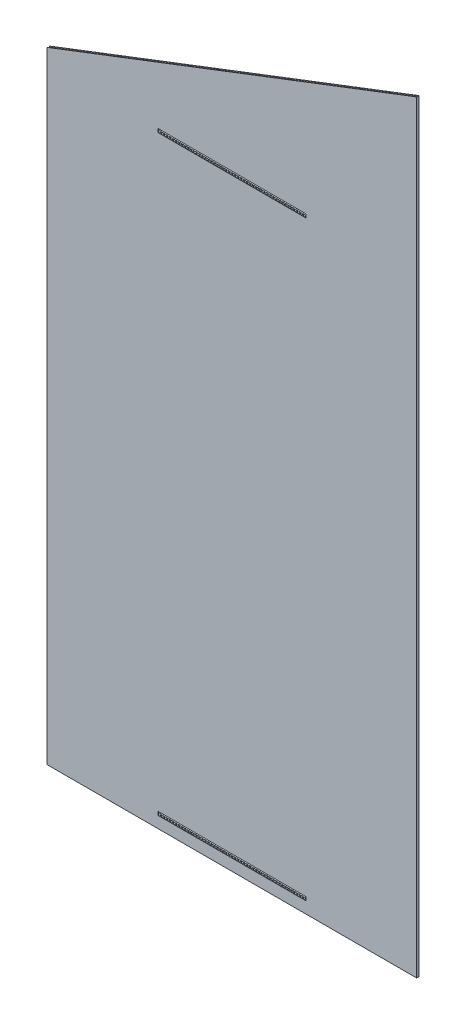
SolidWorks part; units mm, degrees
material "Acrylic (Medium-high impact)"
ref_plane "Front Plane" through (0, 0, 0) normal (0, 0, 1) x (1, 0, 0)
ref_plane "Top Plane" through (0, 0, 0) normal (0, 1, 0) x (1, 0, 0)
ref_plane "Right Plane" through (0, 0, 0) normal (1, 0, 0) x (0, 0, -1)
sketch "Sketch1" plane through (0, 0, 0) normal (0, 1, 0) x (1, 0, 0)
  line L0 (5, -4) -> (-5.3, -4)
  line L1 (-5.3, -4) -> (5, -4) construction
  line L2 (-5, -4) -> (-5, 4) construction
  line L3 (-5.3, 4) -> (5, 4) construction
  line L4 (5, -4) -> (5, 4) construction
  line L5 (-5, -4) -> (5, 4) construction
  line L6 (-5, 4) -> (5, -4) construction
  line L7 (4.7, -3.7) -> (4.7, 3.7)
  line L8 (-5.3, 3.7) -> (4.7, 3.7)
  line L9 (-5.3, -3.7) -> (4.7, -3.7)
  line L10 (5, 4) -> (5, -4)
  line L11 (-5, 4) -> (5, 4) construction
  line L12 (-5, 3.7) -> (5, 3.7) construction
  line L13 (-5, -3.7) -> (5, -3.7) construction
  line L14 (-5, -4) -> (5, -4) construction
  line L15 (5, 4) -> (-5.3, 4)
  line L16 (-5.3, 4) -> (-5.3, -4) construction
  line L17 (-5.3, 4) -> (-5.3, 3.7)
  line L18 (4.7, -4) -> (4.7, 4) construction
  line L19 (-5.3, -3.7) -> (-5.3, -4)
  point P0 (0, 0)
  dimension "D1" = 8
  dimension "D2" = 10
  dimension "D6" = 0.3
  dimension "D3" = 0.3
  dimension "D4" = 0.3
  dimension "D5" = 0.3
extrude "Boss-Extrude1" add sketch "Sketch1" along normal blind 2580.7
pattern_linear "LPattern1" count 125 spacing 10 along (1, 0, 0) of "Boss-Extrude1"
sketch "Sketch2" plane through (0, 0, 4) normal (0, 0, 1) x (1, 0, 0)
  line L0 (1245, 45) -> (-5.3, 45) construction
  line L1 (1245, 2580.7) -> (1245, 0) construction
  line L2 (-5.3, 2580.7) -> (-5.3, 0) construction
  line L3 (-5.3, 0) -> (1245, 0) construction
  line L4 (1245, 51) -> (-5.3, 51) construction
  line L5 (1245, 38.9) -> (-5.3, 38.9) construction
  line L6 (619.85, 38.9) -> (619.85, 51) construction
  line L7 (869.95, 38.9) -> (869.95, 51)
  line L8 (369.75, 38.9) -> (369.75, 51)
  line L9 (369.75, 51) -> (869.95, 51)
  line L10 (869.95, 38.9) -> (369.75, 38.9)
  line L11 (1245, 2580.7) -> (-5.3, 2100.7548)
  line L12 (1245, 51) -> (-5.3, 51) construction
  line L13 (1245, 45) -> (-5.3, 45) construction
  line L14 (-5.3, 2100.7548) -> (1245, 2100.7548) construction
  line L15 (1245, 2100.7548) -> (1245, 2580.7) construction
  line L16 (1245, 2580.7) -> (-5.3, 2580.7)
  line L17 (-5.3, 2580.7) -> (-5.3, 2100.7548)
  dimension "D1" = 45
  dimension "D6" = 69
  dimension "D2" = 6
  dimension "D3" = 12.1
  dimension "D4" = 250.1
  dimension "D5" = 250.1
extrude "Cut-Extrude1" cut sketch "Sketch2" against normal through all
pattern_linear "LPattern2" count 2 spacing 2000 along (0, 1, 0) of "Cut-Extrude1"
